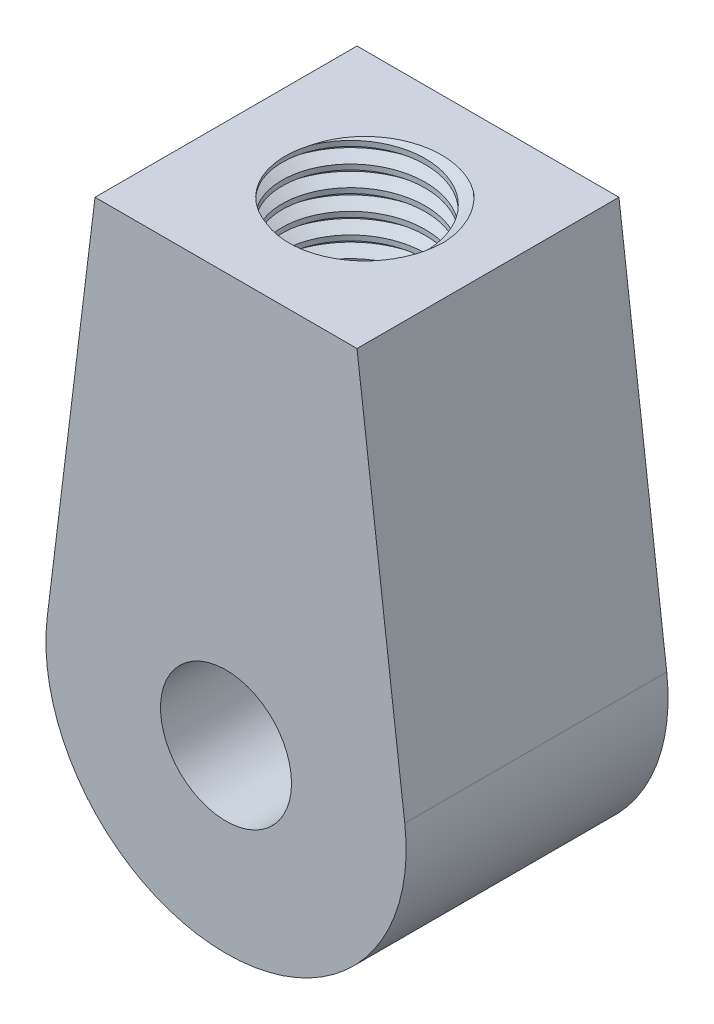
SolidWorks part; units mm, degrees
ref_plane "Front Plane" through (0, 0, 0) normal (0, 0, 1) x (1, 0, 0)
ref_plane "Top Plane" through (0, 0, 0) normal (0, 1, 0) x (1, 0, 0)
ref_plane "Right Plane" through (0, 0, 0) normal (1, 0, 0) x (0, 0, -1)
sketch "Sketch1" plane through (0, 0, 0) normal (0, 0, 1) x (1, 0, 0)
  line L0 (-16, 50) -> (16, 50)
  line L1 (-16, 50) -> (-21.8346, 2.6929)
  line L2 (16, 50) -> (21.8346, 2.6929)
  arc A0 (-21.8346, 2.6929) -> (21.8346, 2.6929) centre (0, 0) ccw
  circle A1 centre (0, 0) radius 8
  dimension "D1" = 44
  dimension "D2" = 16
  dimension "D3" = 32
  dimension "D4" = 16
  dimension "D5" = 50
extrude "Boss-Extrude1" add sketch "Sketch1" along normal mid plane 32
hole_wizard "M20x2.5 Tapped Hole1" positions "Sketch3" profile "Sketch4" tap size "M20x2.5" standard "ANSI Metric"
sketch "Sketch3" plane through (0, 50, 0) normal (0, 1, 0) x (1, 0, 0)
  point P0 (0, 0)
sketch "Sketch4" plane through (0, 50, 0) normal (1, 0, 0) x (0, 0, 1)
  line L0 (0, 0) -> (0, 43.2575)
  line L1 (0, 43.2575) -> (8.75, 38)
  line L2 (8.75, 38) -> (8.75, 0)
  line L5 (8.75, 0) -> (0, 0)
  line L10 (0, 43.2575) -> (-8.75, 38) construction
  line L11 (0, -6.35) -> (0, 107.95) construction
  dimension "Tap Drill Dia." = 17.5
  dimension "Tap Drill Depth" = 38
  dimension "Drill Angle" = 118
cosmetic thread "Hole Thread1" parameters "D1"=34, "D2"=20
thread "Thread1" pitch 2.5 method cut profile "Thread Profile1" start angle 0, offset 2, length 36, pitch 2.5, diameter 17.5
ref_plane "Plane1" through (-8.75, 52, 0) normal (0, 0, 1) x (-1, 0, 0)
sketch "Thread Profile1" plane through (-8.75, 52, 0) normal (0, 0, 1) x (-1, 0, 0)
  line L0 (0, 0) -> (0, 2.5) construction
  line L1 (0, 0) -> (1.3532, 0.7812)
  line L2 (1.3532, 0.7812) -> (1.3532, 1.0937)
  line L3 (1.3532, 1.0937) -> (0, 1.875)
  line L4 (1.3532, 0.9375) -> (0, 0.9375) construction
  line L11 (0, 0) -> (0, 1.875)
  point P2 (0, 0)
  dimension "Pitch" = 2.5
  dimension "Profile_Angle" = 60
  dimension "Profile_Land" = 0.3125
  dimension "Profile_Height" = 1.3532
